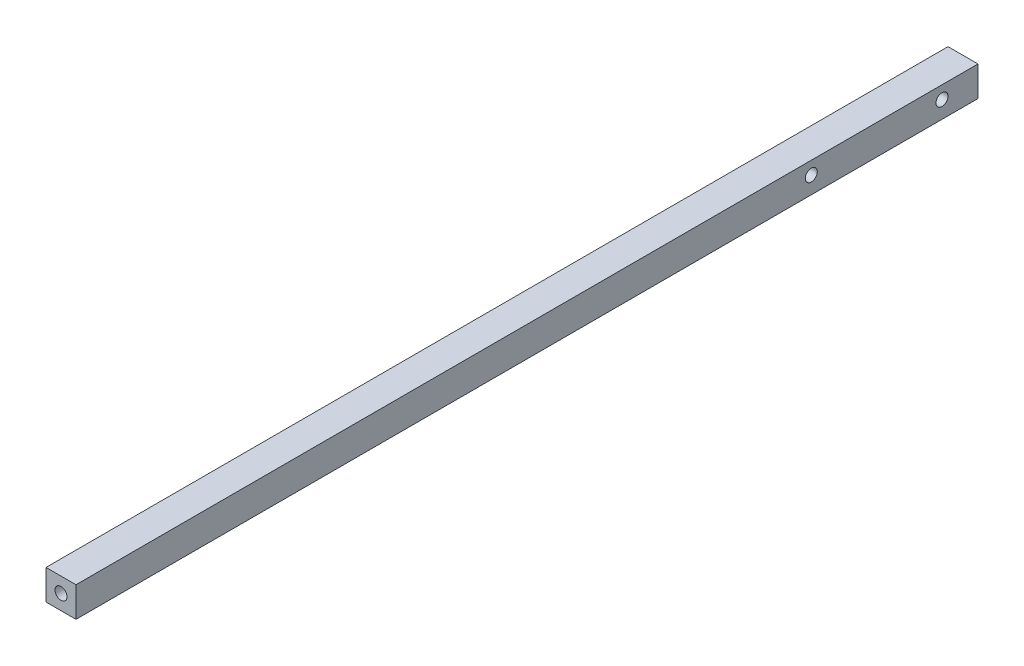
SolidWorks part; units mm, degrees
ref_plane "Plan de face" through (0, 0, 0) normal (0, 0, 1) x (1, 0, 0)
ref_plane "Plan de dessus" through (0, 0, 0) normal (0, 1, 0) x (1, 0, 0)
ref_plane "Plan de droite" through (0, 0, 0) normal (1, 0, 0) x (0, 0, -1)
sketch "Esquisse1" plane through (0, 0, 0) normal (0, 0, 1) x (1, 0, 0)
  line L1 (0, 0) -> (10, 0)
  line L2 (0, 0) -> (0, 10)
  line L3 (0, 10) -> (10, 10)
  line L4 (10, 0) -> (10, 10)
  dimension "D1" = 10
  dimension "D2" = 10
extrude "Boss.-Extru.1" add sketch "Esquisse1" along normal blind 300.81
sketch "Esquisse2" plane through (0, 0, 0) normal (-1, 0, 0) x (0, 0, 1)
  line L0 (63.827, 5.7) -> (-7.5908, 5.7) construction
  line L1 (300.81, 0) -> (0, 0) construction
  line L2 (0, 10) -> (0, 0) construction
  circle A0 centre (12, 5.7) radius 2
  circle A1 centre (55.6, 5.7) radius 2
  dimension "D4" = 4
  dimension "D5" = 4
  dimension "D1" = 5.7
  dimension "D2" = 12
  dimension "D3" = 43.6
extrude "Enlèv. mat.-Extru.1" cut sketch "Esquisse2" against normal through all
sketch "Esquisse3" plane through (0, 0, 0) normal (0, 0, -1) x (-1, 0, 0)
  line L0 (0, 10) -> (0, 0) construction
  line L2 (0, 0) -> (-10, 0) construction
  circle A0 centre (-5, 5) radius 2
  dimension "D1" = 4
  dimension "D2" = 5
  dimension "D3" = 5
extrude "Enlèv. mat.-Extru.2" cut sketch "Esquisse3" against normal blind 6
sketch "Esquisse4" plane through (0, 0, 300.81) normal (0, 0, 1) x (1, 0, 0)
  line L0 (0, 10) -> (0, 0) construction
  line L1 (0, 0) -> (10, 0) construction
  circle A0 centre (5, 5) radius 2
  dimension "D1" = 4
  dimension "D2" = 5
  dimension "D3" = 5
extrude "Enlèv. mat.-Extru.3" cut sketch "Esquisse4" against normal blind 6
